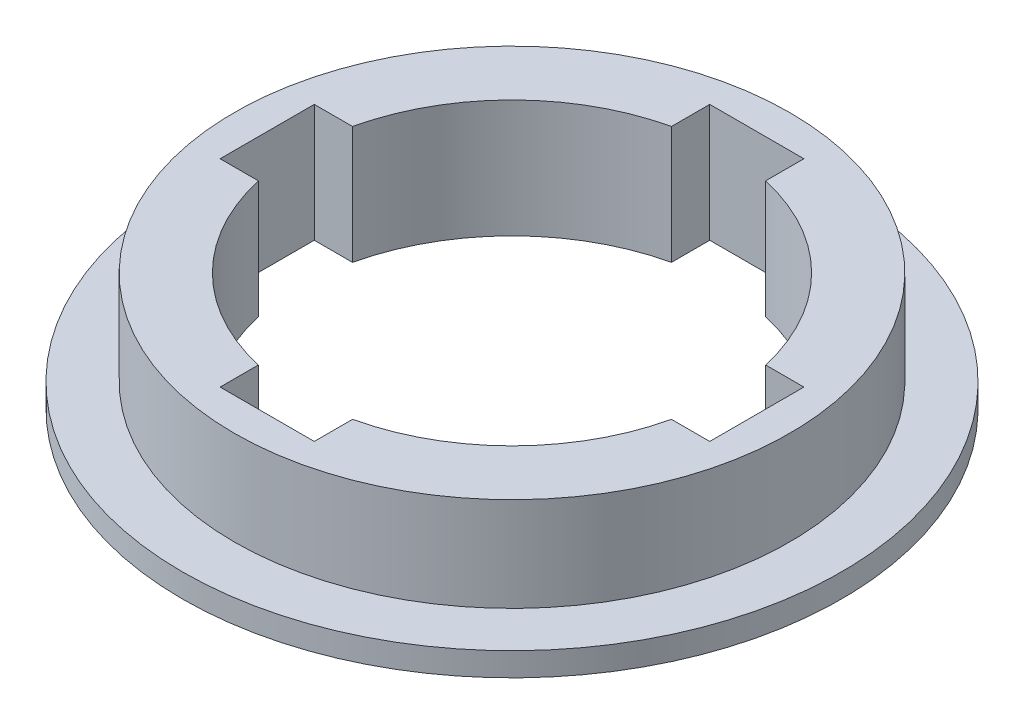
SolidWorks part; units mm, degrees
ref_plane "Front Plane" through (0, 0, 0) normal (0, 0, 1) x (1, 0, 0)
ref_plane "Top Plane" through (0, 0, 0) normal (0, 1, 0) x (1, 0, 0)
ref_plane "Right Plane" through (0, 0, 0) normal (1, 0, 0) x (0, 0, -1)
sketch "Sketch1" plane through (0, 0, 0) normal (0, 1, 0) x (1, 0, 0)
  circle A0 centre (0, 0) radius 35
  circle A1 centre (0, 0) radius 30 construction
  circle A2 centre (0, 0) radius 22.5
  dimension "D1" = 70
  dimension "D2" = 60
  dimension "D3" = 45
extrude "Boss-Extrude1" add sketch "Sketch1" along normal blind 2.5
sketch "Sketch2" plane through (0, 2.5, 0) normal (0, 1, 0) x (1, 0, 0)
  circle A0 centre (0, 0) radius 29.5
  circle A1 centre (0, 0) radius 22.5
  dimension "D1" = 59
  dimension "D2" = 45
extrude "Boss-Extrude2" add sketch "Sketch2" along normal blind 10
sketch "Sketch3" plane through (0, 12.5, 0) normal (0, 1, 0) x (1, 0, 0)
  line L0 (0, 0) -> (-35, 0) construction
  line L1 (0, 0) -> (0, -35) construction
  line L2 (-5, 21.9374) -> (-5, 26)
  line L3 (5, -26) -> (-5, -26)
  line L4 (5, -26) -> (5, -21.9374)
  line L5 (5, 26) -> (-5, 26)
  line L6 (-5, -26) -> (-5, -21.9374)
  line L7 (5, -26) -> (-5, 26) construction
  line L8 (5, 26) -> (-5, -26) construction
  line L9 (26, -5) -> (21.9374, -5)
  line L10 (26, -5) -> (26, 5)
  line L11 (26, 5) -> (21.9374, 5)
  line L12 (-26, -5) -> (-26, 5)
  line L13 (26, -5) -> (-26, 5) construction
  line L14 (26, 5) -> (-26, -5) construction
  line L16 (-21.9374, -5) -> (-26, -5)
  line L17 (-21.9374, 5) -> (-26, 5)
  line L18 (5, 21.9374) -> (5, 26)
  circle A0 centre (0, 0) radius 35 construction
  arc A1 (21.9374, 5) -> (5, 21.9374) centre (0, 0) ccw
  arc A2 (-5, 21.9374) -> (-21.9374, 5) centre (0, 0) ccw
  arc A3 (-21.9374, -5) -> (-5, -21.9374) centre (0, 0) ccw
  arc A4 (5, -21.9374) -> (21.9374, -5) centre (0, 0) ccw
  dimension "D1" = 45
  dimension "D2" = 52
  dimension "D3" = 10
  dimension "D4" = 52
  dimension "D5" = 10
extrude "Cut-Extrude1" cut sketch "Sketch3" against normal through all
